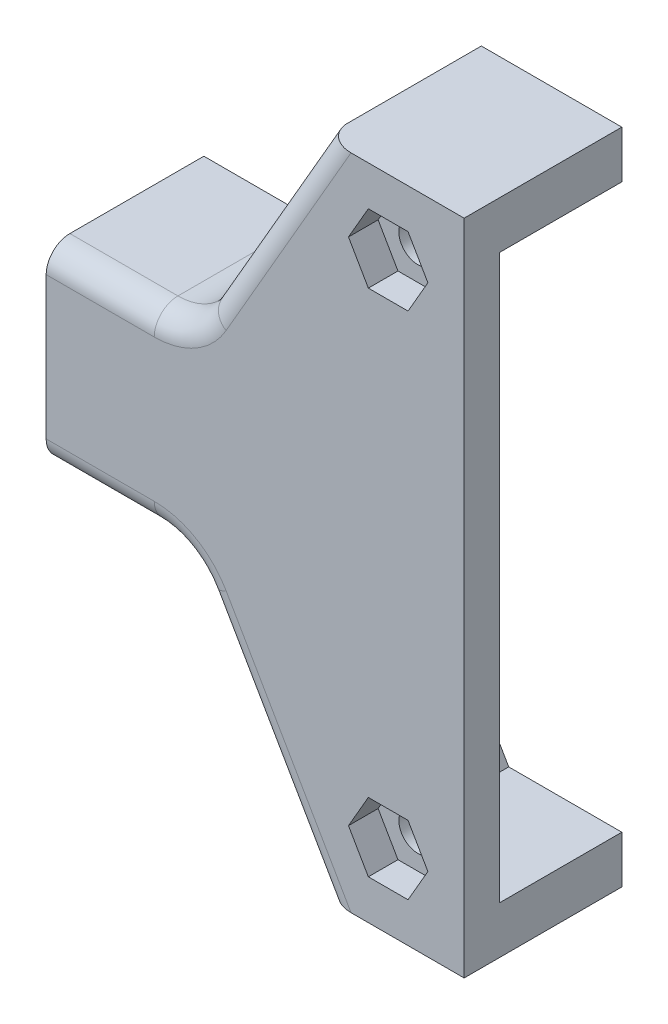
SolidWorks part; units mm, degrees
ref_plane "Спереди" through (0, 0, 0) normal (0, 0, 1) x (1, 0, 0)
ref_plane "Сверху" through (0, 0, 0) normal (0, 1, 0) x (1, 0, 0)
ref_plane "Справа" through (0, 0, 0) normal (1, 0, 0) x (0, 0, -1)
sketch "Эскиз1" plane through (0, 0, 0) normal (0, 0, 1) x (1, 0, 0)
  line L4 (0, 25.75) -> (0, -25.75)
  line L52 (-7.4224, -16) -> (-11.9484, -23.8394)
  line L53 (-11.9484, -23.8394) -> (-10.8453, -25.75)
  line L54 (-10.8453, -25.75) -> (0, -25.75)
  line L66 (0, 25.75) -> (-10.8453, 25.75)
  line L67 (-10.8453, 25.75) -> (-11.9484, 23.8394)
  line L68 (-11.9484, 23.8394) -> (-7.4224, 16)
  line L69 (-6.8865, 14) -> (-6.8865, -14)
  line L70 (-14.8865, -15.0184) -> (-14.8865, 15.0184)
  line L71 (-16.7525, 15.5184) -> (-20.2272, 9.5)
  line L72 (-26.2894, 6) -> (-35.4027, 6)
  line L73 (-35.4027, 6) -> (-35.4027, -6)
  line L74 (-35.4027, -6) -> (-26.2894, -6)
  line L75 (-20.2272, -9.5) -> (-16.7525, -15.5184)
  line L76 (0, -27.75) -> (0, -25.75)
  line L77 (0, -25.75) -> (-10.8453, -25.75)
  line L78 (-10.8453, -25.75) -> (-11.9484, -23.8394)
  line L79 (-11.9484, -23.8394) -> (-7.4224, -16)
  line L80 (-14.8865, -14) -> (-14.8865, -15.0184)
  line L81 (-16.7525, -15.5184) -> (-20.2272, -9.5)
  line L82 (-26.2894, -6) -> (-35.4027, -6)
  line L83 (-35.4027, -6) -> (-35.4027, -8)
  line L84 (-35.4027, -8) -> (-26.2894, -8)
  line L85 (-21.9593, -10.5) -> (-12, -27.75)
  line L86 (-12, -27.75) -> (0, -27.75)
  line L87 (-14.8865, -10.925) -> (-14.8865, -14)
  line L88 (-6.8865, -14) -> (-6.8865, -10.925)
  line L89 (-6.8865, -10.925) -> (-14.8865, -10.925)
  line L90 (-14.8865, 14) -> (-14.8865, 10.925)
  line L91 (-14.8865, 10.925) -> (-6.8865, 10.925)
  line L92 (-6.8865, 10.925) -> (-6.8865, 14)
  line L93 (-35.4027, 8) -> (-35.4027, 6)
  line L94 (-35.4027, 6) -> (-26.2894, 6)
  line L95 (-20.2272, 9.5) -> (-16.7525, 15.5184)
  line L96 (-14.8865, 15.0184) -> (-14.8865, 14)
  line L97 (-7.4224, 16) -> (-11.9484, 23.8394)
  line L98 (-11.9484, 23.8394) -> (-10.8453, 25.75)
  line L99 (-10.8453, 25.75) -> (0, 25.75)
  line L100 (0, 25.75) -> (0, 27.75)
  line L101 (0, 27.75) -> (-12, 27.75)
  line L102 (-12, 27.75) -> (-21.9593, 10.5)
  line L103 (-26.2894, 8) -> (-35.4027, 8)
  arc A16 (-6.8865, 14) -> (-7.4224, 16) centre (-10.8865, 14) ccw
  arc A17 (-7.4224, -16) -> (-6.8865, -14) centre (-10.8865, -14) ccw
  arc A18 (-16.7525, -15.5184) -> (-14.8865, -15.0184) centre (-15.8865, -15.0184) ccw
  arc A19 (-14.8865, 15.0184) -> (-16.7525, 15.5184) centre (-15.8865, 15.0184) ccw
  arc A20 (-26.2894, 6) -> (-20.2272, 9.5) centre (-26.2894, 13) ccw
  arc A21 (-20.2272, -9.5) -> (-26.2894, -6) centre (-26.2894, -13) ccw
  arc A22 (-14.8865, -14) -> (-7.4224, -16) centre (-10.8865, -14) ccw
  arc A23 (-16.7525, -15.5184) -> (-14.8865, -15.0184) centre (-15.8865, -15.0184) ccw
  arc A24 (-20.2272, -9.5) -> (-26.2894, -6) centre (-26.2894, -13) ccw
  arc A25 (-21.9593, -10.5) -> (-26.2894, -8) centre (-26.2894, -13) ccw
  arc A26 (-14.8865, -14) -> (-6.8865, -14) centre (-10.8865, -14) ccw
  arc A27 (-6.8865, 14) -> (-14.8865, 14) centre (-10.8865, 14) ccw
  arc A28 (-26.2894, 6) -> (-20.2272, 9.5) centre (-26.2894, 13) ccw
  arc A29 (-14.8865, 15.0184) -> (-16.7525, 15.5184) centre (-15.8865, 15.0184) ccw
  arc A30 (-7.4224, 16) -> (-14.8865, 14) centre (-10.8865, 14) ccw
  arc A31 (-26.2894, 8) -> (-21.9593, 10.5) centre (-26.2894, 13) ccw
  circle A34 centre (-10.8865, -14) radius 1.6
  circle A35 centre (-10.8865, 14) radius 1.6
sketch "Эскиз3" plane through (0, 0, 0) normal (0, 0, 1) x (1, 0, 0)
  line L0 (-35.4027, -8) -> (-26.2894, -8) construction
  line L1 (-21.9593, -10.5) -> (-12, -27.75) construction
  line L2 (-12, -27.75) -> (0, -27.75) construction
  line L3 (0, 27.75) -> (-12, 27.75) construction
  line L4 (-12, 27.75) -> (-21.9593, 10.5) construction
  line L5 (-26.2894, 8) -> (-35.4027, 8) construction
  line L6 (-35.4027, -8) -> (-26.2894, -8)
  line L7 (-21.9593, -10.5) -> (-12, -27.75)
  line L8 (-12, -27.75) -> (-0.15, -27.75)
  line L9 (-0.15, 27.75) -> (-12, 27.75)
  line L10 (-12, 27.75) -> (-21.9593, 10.5)
  line L11 (-26.2894, 8) -> (-35.4027, 8)
  line L13 (-35.4027, 8) -> (-35.4027, -8)
  line L14 (-0.15, 27.75) -> (-0.15, -27.75)
  line L15 (0, 25.75) -> (0, -25.75) construction
  arc A0 (-21.9593, -10.5) -> (-26.2894, -8) centre (-26.2894, -13) ccw construction
  arc A1 (-26.2894, 8) -> (-21.9593, 10.5) centre (-26.2894, 13) ccw construction
  arc A2 (-21.9593, -10.5) -> (-26.2894, -8) centre (-26.2894, -13) ccw
  arc A3 (-26.2894, 8) -> (-21.9593, 10.5) centre (-26.2894, 13) ccw
  dimension "D1" = 0.15
extrude "Бобышка-Вытянуть1" add sketch "Эскиз3" against normal blind 3
sketch "Эскиз4" plane through (0, 0, -3) normal (0, 0, -1) x (-1, 0, 0)
  line L0 (12, -27.75) -> (0, -27.75) construction
  line L1 (21.9593, -10.5) -> (12, -27.75) construction
  line L2 (35.4027, -8) -> (26.2894, -8) construction
  line L3 (26.2894, 8) -> (35.4027, 8) construction
  line L4 (12, 27.75) -> (21.9593, 10.5) construction
  line L5 (0, 27.75) -> (12, 27.75) construction
  line L18 (12, -27.75) -> (0.15, -27.75)
  line L19 (21.9593, -10.5) -> (12, -27.75)
  line L20 (35.4027, -8) -> (26.2894, -8)
  line L21 (26.2894, 8) -> (35.4027, 8)
  line L22 (12, 27.75) -> (21.9593, 10.5)
  line L23 (0.15, 27.75) -> (12, 27.75)
  line L24 (35.4027, -4) -> (26.2894, -4)
  line L25 (18.4952, -8.5) -> (15.813, -13.1458)
  line L26 (9.6906, -23.75) -> (0.15, -23.75)
  line L27 (0.15, 23.75) -> (9.6906, 23.75)
  line L28 (9.6906, 23.75) -> (12.6099, 18.6936)
  line L29 (26.2894, 4) -> (35.4027, 4)
  line L32 (35.4027, -4) -> (35.4027, -8)
  line L33 (35.4027, 8) -> (35.4027, 4)
  line L34 (0.15, -27.75) -> (0.15, 27.75) construction
  line L35 (0.15, -27.75) -> (0.15, -23.75)
  line L36 (0.15, 23.75) -> (0.15, 27.75)
  line L37 (0, 27.75) -> (12, 27.75) construction
  line L38 (0, 23.75) -> (9.6906, 23.75) construction
  line L39 (15.813, 13.1458) -> (18.4952, 8.5)
  line L40 (9.6906, -23.75) -> (0, -23.75) construction
  line L41 (12, -27.75) -> (0, -27.75) construction
  line L42 (12.6099, -18.6936) -> (9.6906, -23.75)
  line L43 (9.6906, 23.75) -> (18.4952, 8.5) construction
  line L45 (18.4952, -8.5) -> (9.6906, -23.75) construction
  arc A0 (26.2894, -8) -> (21.9593, -10.5) centre (26.2894, -13) ccw construction
  arc A1 (21.9593, 10.5) -> (26.2894, 8) centre (26.2894, 13) ccw construction
  arc A5 (26.2894, -8) -> (21.9593, -10.5) centre (26.2894, -13) ccw
  arc A6 (21.9593, 10.5) -> (26.2894, 8) centre (26.2894, 13) ccw
  arc A7 (26.2894, -4) -> (18.4952, -8.5) centre (26.2894, -13) ccw
  arc A8 (18.4952, 8.5) -> (26.2894, 4) centre (26.2894, 13) ccw
  arc A9 (15.813, 13.1458) -> (12.6099, 18.6936) centre (10.8865, 14) ccw
  arc A10 (12.6099, -18.6936) -> (15.813, -13.1458) centre (10.8865, -14) ccw
  dimension "D2" = 5
  dimension "D1" = 4
extrude "Бобышка-Вытянуть2" add sketch "Эскиз4" along normal blind 10.3
sketch "Эскиз5" plane through (0, 0, -13.3) normal (0, 0, -1) x (-1, 0, 0)
  line L0 (26.2894, -6) -> (35.4027, -6) construction
  line L1 (16.7525, -15.5184) -> (20.2272, -9.5) construction
  line L2 (0, -25.75) -> (10.8453, -25.75) construction
  line L3 (0, 25.75) -> (10.8453, 25.75) construction
  line L4 (16.7525, 15.5184) -> (20.2272, 9.5) construction
  line L5 (26.2894, 6) -> (35.4027, 6) construction
  line L6 (18.4952, -8.5) -> (16.4952, -11.9641)
  line L7 (18.0973, -12.8891) -> (16.4952, -11.9641)
  line L8 (9.6906, 23.75) -> (0.15, 23.75)
  line L9 (0.15, 23.75) -> (0.15, -23.75)
  line L10 (0.15, -23.75) -> (9.6906, -23.75)
  line L11 (15.813, -13.1458) -> (18.4952, -8.5)
  line L12 (26.2894, -4) -> (35.4027, -4)
  line L13 (35.4027, -4) -> (35.4027, 4)
  line L14 (35.4027, 4) -> (26.2894, 4)
  line L15 (12.6099, 18.6936) -> (9.6906, 23.75)
  line L16 (2.15, 23.75) -> (0.15, 23.75) construction
  line L22 (32.4027, 4) -> (26.2894, 4)
  line L25 (0.15, -25.6) -> (0.15, -23.75) construction
  line L26 (26.2894, -5.85) -> (32.4027, -5.85)
  line L27 (18.0973, -12.8891) -> (20.0973, -9.425)
  line L28 (0.15, -25.6) -> (2.15, -25.6) construction
  line L30 (32.4027, -4) -> (26.2894, -4)
  line L31 (2.15, -23.75) -> (0.15, -23.75) construction
  line L32 (32.4027, 5.85) -> (32.4027, 4)
  line L33 (35.4027, 4) -> (35.4027, -4) construction
  line L34 (32.4027, -4) -> (32.4027, -5.85)
  line L35 (26.2894, 5.85) -> (35.4027, 5.85) construction
  line L36 (35.4027, -4) -> (26.2894, -4) construction
  line L37 (2.15, 25.6) -> (2.15, 23.75) construction
  line L38 (2.15, -23.75) -> (2.15, -25.6) construction
  line L39 (9.6906, -23.75) -> (0.15, -23.75) construction
  line L41 (0, 0) -> (35.4027, 0) construction
  line L43 (0, 25.75) -> (10.8453, 25.75) construction
  line L44 (16.7525, 15.5184) -> (20.2272, 9.5) construction
  line L45 (26.2894, 6) -> (35.4027, 6) construction
  line L46 (0.15, 25.6) -> (2.15, 25.6) construction
  line L47 (18.0973, 12.8891) -> (20.0973, 9.425)
  line L48 (26.2894, 5.85) -> (32.4027, 5.85)
  line L49 (35.4027, 6) -> (35.4027, -6) construction
  line L50 (0.15, 25.6) -> (0.15, 23.75) construction
  line L54 (18.0973, 12.8891) -> (16.4952, 11.9641)
  line L55 (0, 25.6) -> (10.8453, 25.6) construction
  line L57 (16.6226, 15.4434) -> (20.0973, 9.425) construction
  line L69 (0.15, 27.75) -> (0.15, 23.75) construction
  line L101 (9.6906, -23.75) -> (12.6099, -18.6936)
  line L103 (18.4952, 8.5) -> (15.813, 13.1458)
  line L104 (18.4952, 8.5) -> (16.4952, 11.9641)
  arc A0 (20.2272, -9.5) -> (26.2894, -6) centre (26.2894, -13) cw construction
  arc A1 (20.2272, 9.5) -> (26.2894, 6) centre (26.2894, 13) ccw construction
  arc A2 (26.2894, -4) -> (18.4952, -8.5) centre (26.2894, -13) ccw
  arc A3 (18.4952, 8.5) -> (26.2894, 4) centre (26.2894, 13) ccw
  arc A5 (18.4952, 8.5) -> (26.2894, 4) centre (26.2894, 13) ccw
  arc A6 (20.0973, -9.425) -> (26.2894, -5.85) centre (26.2894, -13) cw
  arc A7 (18.4952, -8.5) -> (26.2894, -4) centre (26.2894, -13) cw
  arc A13 (20.2272, 9.5) -> (26.2894, 6) centre (26.2894, 13) ccw construction
  arc A14 (20.0973, 9.425) -> (26.2894, 5.85) centre (26.2894, 13) ccw
  arc A25 (12.6099, -18.6936) -> (15.813, -13.1458) centre (10.8865, -14) ccw
  arc A27 (15.813, 13.1458) -> (12.6099, 18.6936) centre (10.8865, 14) ccw
  dimension "D3" = 4
  dimension "D4" = 3
  dimension "D5" = 2
  dimension "D1" = 0
  dimension "D2" = 0.15
extrude "Бобышка-Вытянуть3" add sketch "Эскиз5" along normal blind 1.8
fillet "Скругление1" radius 2 6 edges at (-16.9796, -19.125, 0) (-23.7894, -8.6699, 0) (-30.846, 8, 0) (-23.7894, 8.6699, 0) (-30.846, -8, 0) (-16.9796, 19.125, 0)
sketch "Эскиз6" plane through (0, 0, 0) normal (0, 0, 1) x (1, 0, 0)
  line L0 (0, 0) -> (-35.4027, 0) construction
  line L1 (-8.2307, 24.4) -> (-9.905, 21.5)
  line L2 (-9.905, 21.5) -> (-8.2307, 18.6)
  line L3 (-8.2307, 18.6) -> (-4.882, 18.6)
  line L4 (-4.882, 18.6) -> (-3.2077, 21.5)
  line L5 (-3.2077, 21.5) -> (-4.882, 24.4)
  line L6 (-4.882, 24.4) -> (-8.2307, 24.4)
  line L7 (-35.4027, 6) -> (-35.4027, -6) construction
  line L8 (-6.5563, 21.5) -> (-6.5563, 0) construction
  line L9 (-10.8865, 14) -> (-6.5563, 21.5) construction
  line L10 (-9.6906, 27.75) -> (-20.2272, 9.5) construction
  line L11 (-4.882, -24.4) -> (-8.2307, -24.4)
  line L12 (-3.2077, -21.5) -> (-4.882, -24.4)
  line L13 (-4.882, -18.6) -> (-3.2077, -21.5)
  line L14 (-8.2307, -18.6) -> (-4.882, -18.6)
  line L15 (-9.905, -21.5) -> (-8.2307, -18.6)
  line L16 (-8.2307, -24.4) -> (-9.905, -21.5)
  line L17 (0, 25.75) -> (0, -25.75) construction
  circle A0 centre (-6.5563, 21.5) radius 2.9 construction
  circle A1 centre (-6.5563, -21.5) radius 2.9 construction
  dimension "D1" = 5.8
  dimension "D2" = 21.5
  dimension "D3" = 6.5563
extrude "Вырез-Вытянуть1" cut sketch "Эскиз6" against normal blind 2.5
sketch "Эскиз7" plane through (0, 0, 0) normal (0, 0, 1) x (1, 0, 0)
  circle A0 centre (-6.5563, 21.5) radius 1.6
  circle A1 centre (-6.5563, -21.5) radius 1.6
  dimension "D1" = 3.2
extrude "Вырез-Вытянуть2" cut sketch "Эскиз7" against normal up to next
sketch "Эскиз8" plane through (0, 0, -3) normal (0, 0, -1) x (-1, 0, 0)
  line L1 (11.9484, 23.8394) -> (7.4224, 16) construction
  line L2 (9.5874, 19.75) -> (10.7937, 21.8394)
  line L3 (9.6906, 23.75) -> (12.6099, 18.6936) construction
  line L4 (10.7937, 21.8394) -> (9.6906, 23.75)
  line L5 (9.6906, 23.75) -> (3.0563, 23.75)
  line L6 (0.15, 23.75) -> (9.6906, 23.75) construction
  line L7 (3.0563, 23.75) -> (3.0563, 21.5)
  line L8 (0, 0) -> (35.4027, 0) construction
  line L9 (35.4027, 6) -> (35.4027, -6) construction
  line L10 (3.0563, -23.75) -> (3.0563, -21.5)
  line L11 (9.6906, -23.75) -> (3.0563, -23.75)
  line L12 (10.7937, -21.8394) -> (9.6906, -23.75)
  line L13 (9.5874, -19.75) -> (10.7937, -21.8394)
  arc A0 (3.0563, 21.5) -> (9.5874, 19.75) centre (6.5563, 21.5) ccw
  arc A2 (3.0563, -21.5) -> (9.5874, -19.75) centre (6.5563, -21.5) cw
  circle A3 centre (6.5563, -21.5) radius 1.6 construction
  circle A4 centre (6.5563, 21.5) radius 1.6 construction
  circle A5 centre (6.5563, -21.5) radius 1.6
  circle A6 centre (6.5563, 21.5) radius 1.6
extrude "Бобышка-Вытянуть4" add sketch "Эскиз8" along normal blind 2.5
chamfer "Фаска1" distance 2.5 angle 45 6 edges at (-10.1906, -20.7947, -3) (-3.0563, -22.625, -3) (-5.6505, -18.1193, -3) (-3.0563, 22.625, -3) (-10.1906, 20.7947, -3) (-5.6505, 18.1193, -3)
sketch "Эскиз10" plane through (-35.4027, 0, 0) normal (-1, 0, 0) x (0, 0, 1)
  line L0 (-3, 4) -> (-3, -4) construction
  line L1 (-10.3, 0) -> (-3, 0) construction
  line L5 (-10.3, 4) -> (-3, 4)
  line L6 (-3, 4) -> (-3, -4)
  line L7 (-3, -4) -> (-10.3, -4)
  line L12 (-10.3, -3.9) -> (-10.3, -4)
  line L13 (-10.3, 3.9) -> (-10.3, 4)
  line L14 (-13.3, -4) -> (-3, -4) construction
  arc A0 (-10.3, -3.9) -> (-10.3, 3.9) centre (-10.3, 0) ccw
  point P2 (-3, 0)
  dimension "D2" = 7.8
  dimension "D1" = 7.3
extrude "Бобышка-Вытянуть5" add sketch "Эскиз10" against normal blind 8
